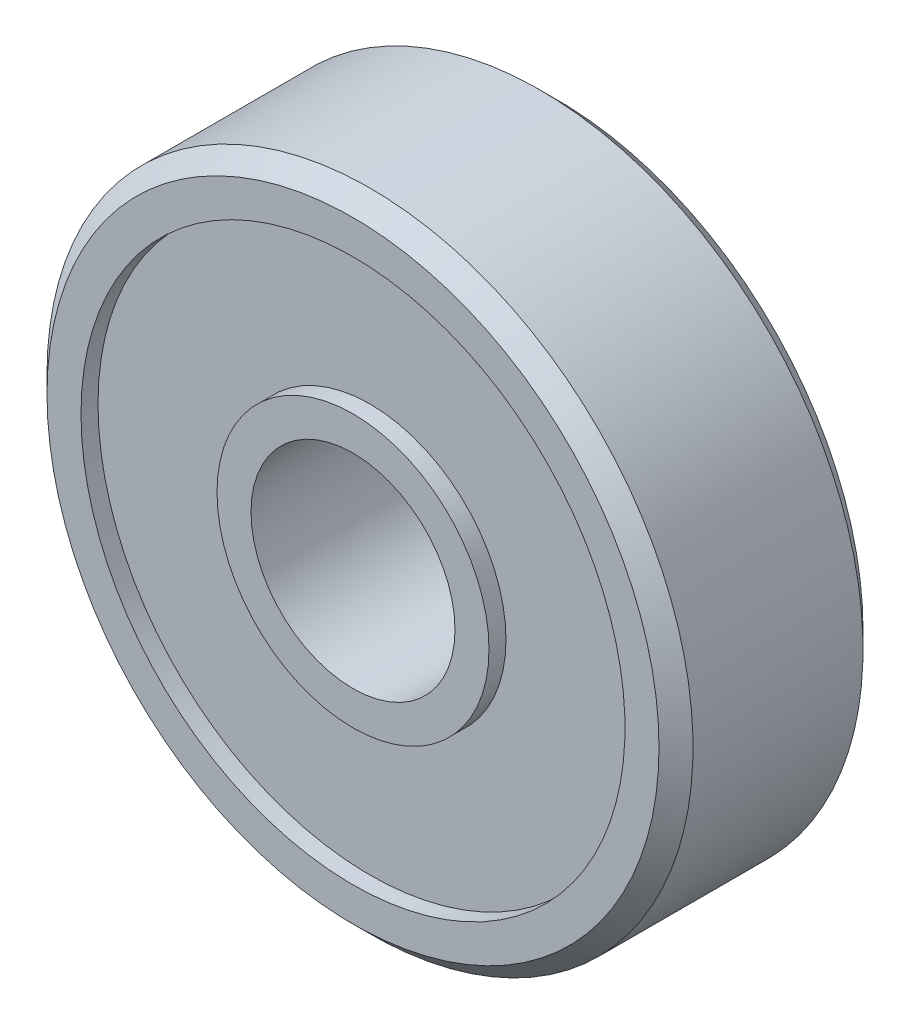
SolidWorks part; units mm, degrees
ref_plane "Front Plane" through (0, 0, 0) normal (0, 0, 1) x (1, 0, 0)
ref_plane "Top Plane" through (0, 0, 0) normal (0, 1, 0) x (1, 0, 0)
ref_plane "Right Plane" through (0, 0, 0) normal (1, 0, 0) x (0, 0, -1)
ref_plane "Plane1" through (0, 0, 0) normal (0, -1, 0) x (1, 0, 0)
sketch "Sketch1" plane through (0, 0, 0) normal (0, -1, 0) x (1, 0, 0)
  line L0 (9.5, 1) -> (9, 1.5)
  line L1 (9, 1.5) -> (8, 1.5)
  line L2 (8, 1.5) -> (8, 1)
  line L3 (8, 1) -> (4, 1)
  line L4 (4, 1) -> (4, 1.5)
  line L5 (4, 1.5) -> (3, 1.5)
  line L6 (3, 1.5) -> (3, -4.5)
  line L7 (3, -4.5) -> (4, -4.5)
  line L8 (4, -4.5) -> (4, -4)
  line L9 (4, -4) -> (8, -4)
  line L10 (8, -4) -> (8, -4.5)
  line L11 (8, -4.5) -> (9, -4.5)
  line L12 (9, -4.5) -> (9.5, -4)
  line L13 (9.5, -4) -> (9.5, 1)
  line L14 (0, 0.5) -> (0, -4.5) construction
  dimension "D1" = 6
  dimension "D2" = 0.5
  dimension "D3" = 8
  dimension "D4" = 6
  dimension "D5" = 0.5
  dimension "D6" = 45
  dimension "D7" = 0.5
  dimension "D8" = 45
  dimension "D9" = 16
  dimension "D10" = 19
revolve "Revolve1" add sketch "Sketch1" angle 360 about L14 reverse direction yes
